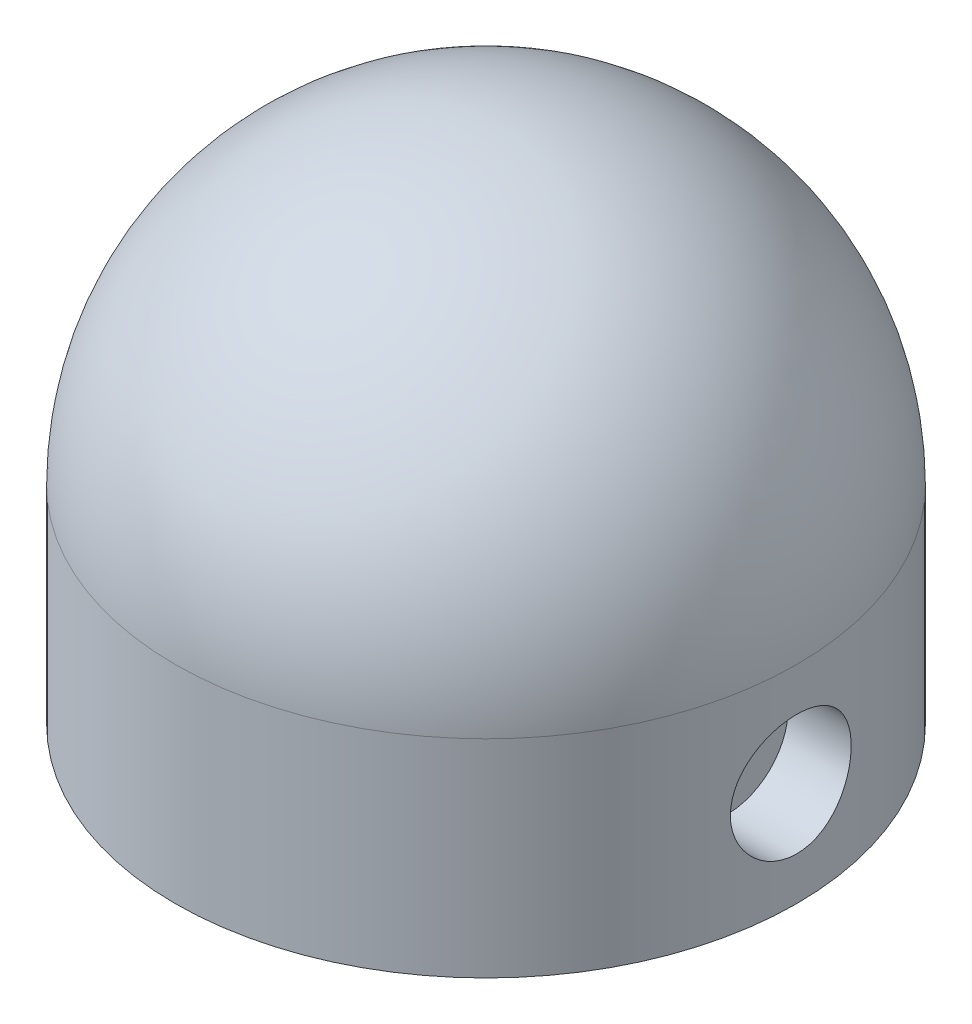
SolidWorks part; units mm, degrees
ref_plane "Спереди" through (0, 0, 0) normal (0, 0, 1) x (1, 0, 0)
ref_plane "Сверху" through (0, 0, 0) normal (0, 1, 0) x (1, 0, 0)
ref_plane "Справа" through (0, 0, 0) normal (1, 0, 0) x (0, 0, -1)
sketch "Sketch1" plane through (0, 0, 0) normal (0, 1, 0) x (1, 0, 0)
  circle A0 centre (0, 0) radius 18
  dimension "D1" = 36
extrude "Boss-Extrude1" add sketch "Sketch1" along normal blind 30
fillet "Fillet1" radius 18 1 edges at (0, 30, 18)
sketch "Sketch2" plane through (0, 0, 0) normal (0, -1, 0) x (1, 0, 0)
  line L1 (-5, 5) -> (5, 5)
  line L2 (-5, 5) -> (-5, -5)
  line L3 (-5, -5) -> (5, -5)
  line L4 (5, 5) -> (5, -5)
  line L5 (-5, 5) -> (5, -5) construction
  line L6 (-5, -5) -> (5, 5) construction
  point P0 (0, 0)
  dimension "D1" = 10
extrude "Cut-Extrude1" cut sketch "Sketch2" against normal blind 25
sketch "Sketch3" plane through (5, 0, 0) normal (-1, 0, 0) x (0, 0, 1)
  line L0 (0, 0) -> (0, 6) construction
  line L1 (-5, 0) -> (5, 0) construction
  circle A0 centre (0, 6) radius 1.6
  dimension "D1" = 3.2
  dimension "D2" = 6
extrude "Cut-Extrude2" cut sketch "Sketch3" against normal through all both and the other way through all
sketch "Sketch4" plane through (5, 0, 0) normal (-1, 0, 0) x (0, 0, 1)
  circle A0 centre (0, 6) radius 3.5
  dimension "D1" = 7
extrude "Cut-Extrude3" cut sketch "Sketch4" against normal blind 20 from offset 9 offset against normal yes
sketch "Sketch5" plane through (-5, 0, 0) normal (1, 0, 0) x (0, 0, -1)
  line L0 (-5, 25) -> (-5, 0) construction
  line L1 (-2.8146, 7.625) -> (-2.8146, 4.375)
  line L2 (-2.8146, 4.375) -> (0, 2.75)
  line L3 (0, 2.75) -> (2.8146, 4.375)
  line L4 (2.8146, 4.375) -> (2.8146, 7.625)
  line L5 (2.8146, 7.625) -> (0, 9.25)
  line L6 (0, 9.25) -> (-2.8146, 7.625)
  circle A0 centre (0, 6) radius 3.25 construction
  dimension "D1" = 6.5
extrude "Cut-Extrude4" cut sketch "Sketch5" against normal blind 16 from offset 8 offset against normal yes
